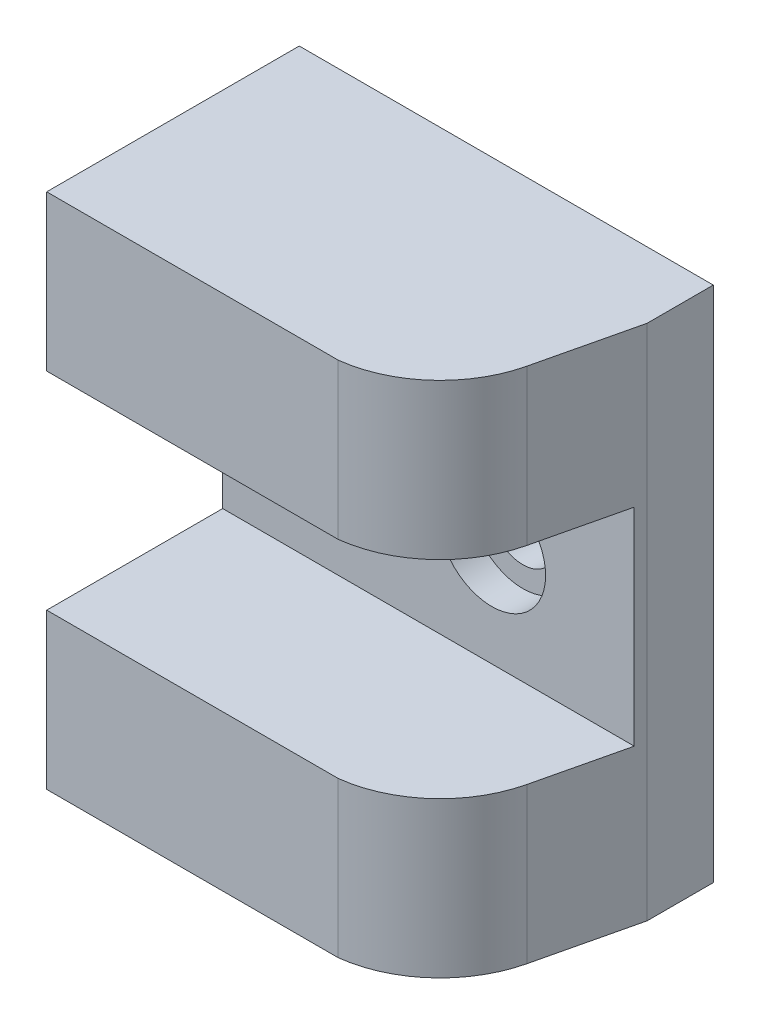
SolidWorks part; units mm, degrees
ref_plane "前视基准面" through (0, 0, 0) normal (0, 0, 1) x (1, 0, 0)
ref_plane "上视基准面" through (0, 0, 0) normal (0, 1, 0) x (1, 0, 0)
ref_plane "右视基准面" through (0, 0, 0) normal (1, 0, 0) x (0, 0, -1)
sketch "草图1" plane through (0, 0, 0) normal (0, 0, 1) x (1, 0, 0)
  line L0 (127, 105) -> (127, -105) construction
  line L1 (127, 80) -> (107, 80)
  line L2 (127, 80) -> (127, 105)
  line L4 (107, 80) -> (107, 105)
  line L5 (72, 105) -> (127, 105) construction
  line L6 (127, 105) -> (107, 105)
  dimension "D1" = 20
  dimension "D2" = 25
extrude "凸台-拉伸1" add sketch "草图1" along normal blind 12.2
sketch "草图2" plane through (0, 105, 0) normal (0, 1, 0) x (1, 0, 0)
  line L0 (127, -12.2) -> (127, 0) construction
  line L6 (125.8906, -7.896) -> (127, -3.196)
  line L8 (127, -3.196) -> (127, -12.2)
  line L10 (127, -12.2) -> (121.083, -12.2)
  line L11 (127, -12.2) -> (107, -12.2) construction
  arc A1 (121.083, -12.2) -> (125.8906, -7.896) centre (120.4, -6.6) ccw
  point P0 (127, -2.3131)
  dimension "D1" = 5.917
  dimension "D2" = 5.6
  dimension "D3" = 6.6
  dimension "D4" = 4.7
extrude "切除-拉伸1" cut sketch "草图2" against normal blind 26.5
sketch "草图3" plane through (0, 0, 12.2) normal (0, 0, 1) x (1, 0, 0)
  line L0 (107, 92.5) -> (127, 92.5) construction
  line L1 (107, 105) -> (107, 80) construction
  line L4 (107, 97.5) -> (127, 97.5)
  line L5 (107, 97.5) -> (107, 87.5)
  line L6 (107, 87.5) -> (127, 87.5)
  line L7 (127, 97.5) -> (127, 87.5)
  line L8 (107, 97.5) -> (127, 87.5) construction
  line L9 (107, 87.5) -> (127, 97.5) construction
  point P6 (117, 92.5)
  dimension "D1" = 10
  dimension "D2" = 20
extrude "切除-拉伸2" cut sketch "草图3" against normal blind 8.5
sketch "草图4" plane through (0, 0, 3.7) normal (0, 0, 1) x (1, 0, 0)
  line L0 (107, 92.5) -> (126.881, 92.5) construction
  line L1 (107, 97.5) -> (107, 87.5) construction
  line L2 (126.881, 87.5) -> (126.881, 97.5) construction
  circle A0 centre (112, 92.5) radius 1.5
  circle A2 centre (120, 92.5) radius 1.5
  dimension "D1" = 3
  dimension "D2" = 8
  dimension "D3" = 5
hole_wizard "M3 六角头螺栓的柱形沉头孔1" positions "草图7" profile "草图8" counterbore size "M3" standard "GB" end condition through all
sketch "草图7" plane through (0, 0, 3.7) normal (0, 0, 1) x (1, 0, 0)
  point P0 (112, 92.5)
  point P3 (120, 92.5)
sketch "草图8" plane through (112, 92.5, 3.7) normal (1, 0, 0) x (0, -1, 0)
  line L0 (0, 0) -> (0, 3.7)
  line L1 (0, 3.7) -> (1.6, 3.7)
  line L3 (1.6, 3.7) -> (1.6, 1.5)
  line L4 (1.6, 1.5) -> (2.6, 1.5)
  line L5 (2.6, 1.5) -> (2.6, 0)
  line L7 (2.6, 0) -> (0, 0)
  line L11 (0, -6.35) -> (0, 107.95) construction
  dimension "通孔孔直径" = 3.2
  dimension "通孔孔深度" = 3.7
  dimension "柱形沉头孔直径" = 5.2
  dimension "柱形沉头孔深度" = 1.5
move or copy body "实体-移动/复制1" [suppressed] bodies to move or copy 109
